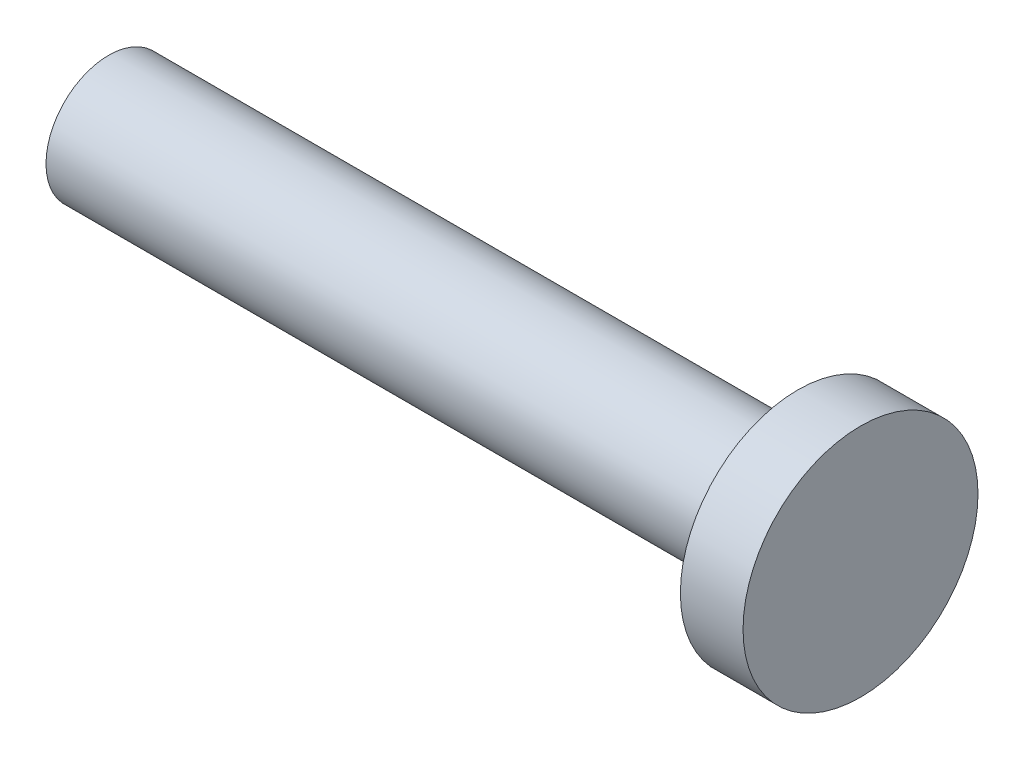
SolidWorks part; units mm, degrees
ref_plane "Front Plane" through (0, 0, 0) normal (0, 0, 1) x (1, 0, 0)
ref_plane "Top Plane" through (0, 0, 0) normal (0, 1, 0) x (1, 0, 0)
ref_plane "Right Plane" through (0, 0, 0) normal (1, 0, 0) x (0, 0, -1)
sketch "Sketch1" plane through (0, 0, 0) normal (0, 0, 1) x (1, 0, 0)
  line L0 (-150.2274, 0) -> (-139.2274, 0)
  line L1 (-139.2274, 0) -> (-139.2274, 1)
  line L2 (-139.2274, 1) -> (-150.2274, 1)
  line L3 (-150.2274, 1) -> (-150.2274, 0)
  dimension "D1" = 11
  dimension "D2" = 1
revolve "Revolve1" add sketch "Sketch1" angle 360 about L0
sketch "Sketch2" plane through (-139.2274, 0, 0) normal (1, 0, 0) x (0, 0, -1)
  circle A0 centre (0, 0) radius 1.875
  dimension "D1" = 3.75
extrude "Boss-Extrude1" add sketch "Sketch2" along normal blind 1
